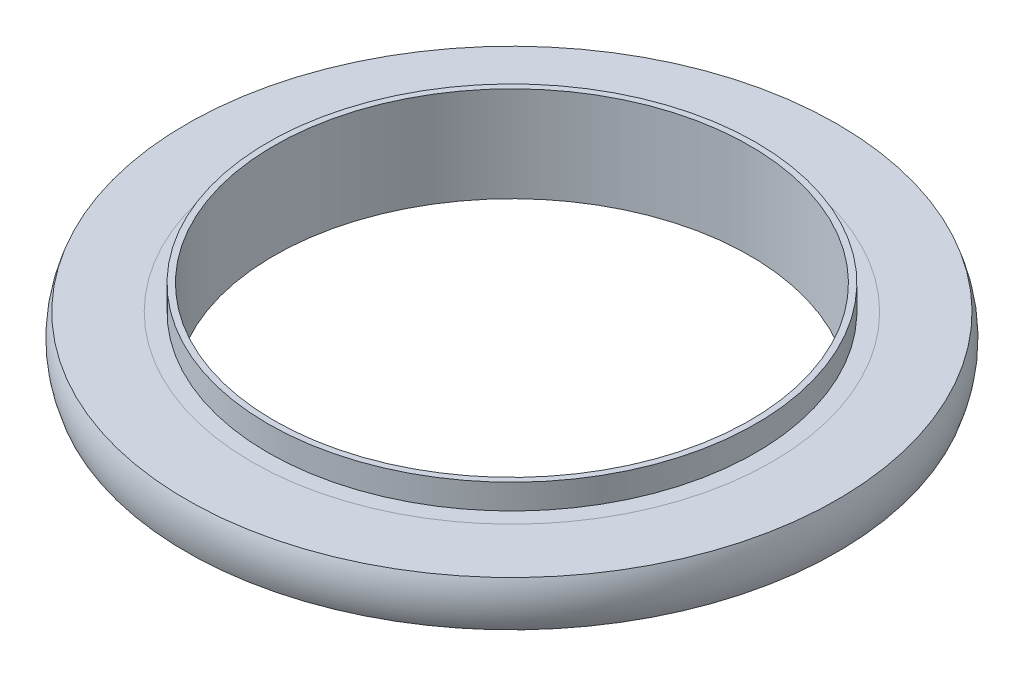
SolidWorks part; units mm, degrees
material "AISI 304"
ref_plane "Front Plane" through (0, 0, 0) normal (0, 0, 1) x (1, 0, 0)
ref_plane "Top Plane" through (0, 0, 0) normal (0, 1, 0) x (1, 0, 0)
ref_plane "Right Plane" through (0, 0, 0) normal (1, 0, 0) x (0, 0, -1)
sketch "Sketch1" plane through (0, 0, 0) normal (0, 0, 1) x (1, 0, 0)
  line L0 (0, 4) -> (0, -4) construction
  line L1 (20, 4) -> (20, -4)
  line L2 (20, -4) -> (20.5, -4)
  line L3 (20.5, -4) -> (20.5, -1.905)
  line L4 (20.5, -1.905) -> (21.8542, -1.905)
  line L5 (20, 4) -> (20.5, 4)
  line L6 (20.5, 4) -> (20.5, 1.905)
  line L7 (20.5, 1.905) -> (21.8542, 1.905)
  arc A0 (21.8542, 1.905) -> (21.8542, -1.905) centre (26.8, 0) ccw
  dimension "D5" = 5.3
  dimension "D1" = 8
  dimension "D2" = 3.81
  dimension "InnerD" = 40
  dimension "LipD" = 41
  dimension "SealD" = 43
revolve "Revolve1" add sketch "Sketch1" angle 360 about L0
sketch "Sketch2" plane through (0, 0, 0) normal (0, 0, 1) x (1, 0, 0)
  line L0 (21.8542, 1.905) -> (27.3458, 1.905)
  line L1 (21.8542, -1.905) -> (27.3458, -1.905)
  line L2 (24.6, 1.905) -> (24.6, -1.905) construction
  line L4 (24.6, 0) -> (24.2, 0) construction
  line L5 (0, -4) -> (0, 4) construction
  arc A0 (21.8542, 1.905) -> (21.8542, -1.905) centre (26.8, 0) ccw construction
  arc A1 (21.8542, 1.905) -> (21.8542, -1.905) centre (26.8, 0) ccw
  arc A2 (27.3458, 1.905) -> (27.3458, -1.905) centre (22.4, 0) cw
  circle A3 centre (24.2, 0) radius 2.7 construction
  dimension "D1" = 5.4
  dimension "D2" = 6.2
revolve "Revolve2" add sketch "Sketch2" angle 360 about L5
ref_axis "Axis1" through (0, -4, 0) along (0, 1, 0)
